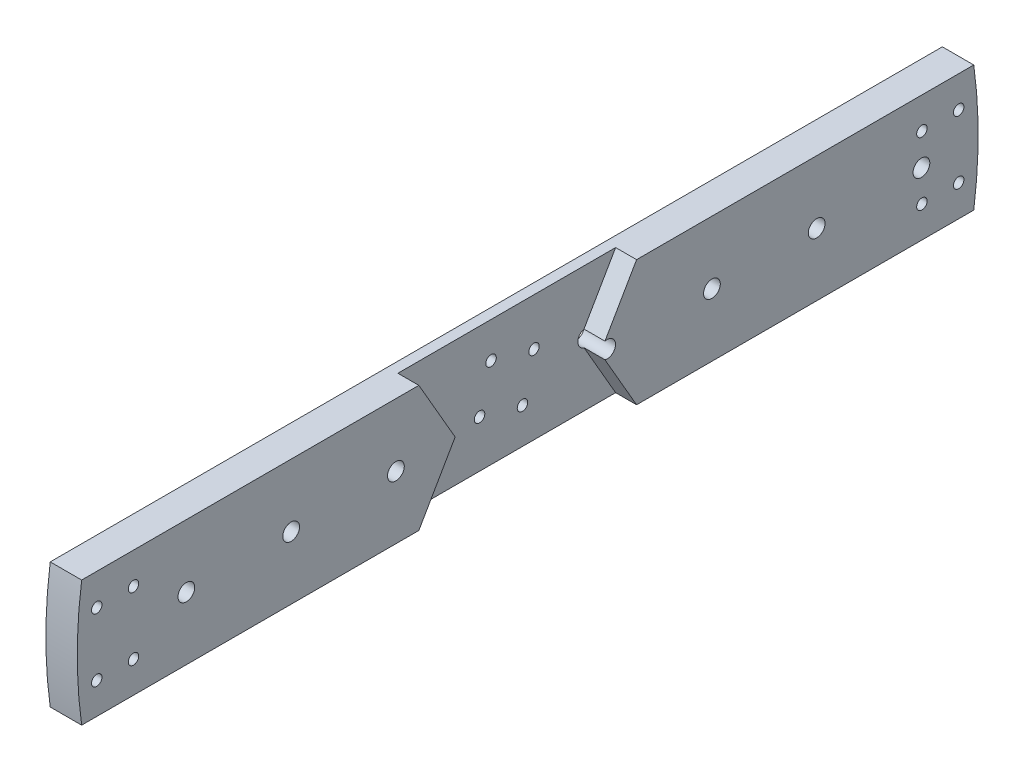
SolidWorks part; units mm, degrees
ref_plane "Front Plane" through (0, 0, 0) normal (0, 0, 1) x (1, 0, 0)
ref_plane "Top Plane" through (0, 0, 0) normal (0, 1, 0) x (1, 0, 0)
ref_plane "Right Plane" through (0, 0, 0) normal (1, 0, 0) x (0, 0, -1)
sketch "Sketch1" plane through (0, 0, 0) normal (1, 0, 0) x (0, 0, -1)
  circle A0 centre (0, 0) radius 273.05
  point P0 (0, 0)
  dimension "D1" = 546.1
curve "Helix/Spiral1"
sketch "Sketch2" plane through (0, 0, 0) normal (1, 0, 0) x (0, 0, -1)
  line L0 (-273.05, 0) -> (273.05, 0) construction
  line L1 (-270.3788, -38.1) -> (270.3788, -38.1)
  line L3 (-270.3788, 38.1) -> (270.3788, 38.1)
  line L4 (270.3788, -38.1) -> (270.3788, 38.1) construction
  line L5 (-270.3788, -38.1) -> (270.3788, 38.1) construction
  line L6 (-270.3788, 38.1) -> (270.3788, -38.1) construction
  line L7 (273.05, 0) -> (228.6, 0) construction
  line L8 (38.1, -38.1) -> (-38.1, -38.1)
  line L9 (38.1, -38.1) -> (38.1, 38.1)
  line L10 (38.1, 38.1) -> (-38.1, 38.1)
  line L11 (-38.1, -38.1) -> (-38.1, 38.1)
  line L12 (38.1, -38.1) -> (-38.1, 38.1) construction
  line L13 (38.1, 38.1) -> (-38.1, -38.1) construction
  line L14 (226.3636, 31.8977) -> (270.3788, 38.1)
  line L15 (0, 0) -> (65.9911, 38.1)
  line L16 (273.05, 0) -> (250.825, 0)
  line L17 (250.825, 0) -> (228.6, 0)
  line L20 (0, 38.1) -> (0, -38.1) construction
  circle A0 centre (0, 0) radius 273.05 construction
  circle A3 centre (175.1536, 0) radius 5.08
  circle A4 centre (111.6538, 0) radius 5.08
  circle A6 centre (-79.9039, 0) radius 5.08
  circle A7 centre (-143.4037, 0) radius 5.08
  circle A8 centre (-206.9035, 0) radius 5.08
  circle A9 centre (0, 0) radius 273.05
  circle A10 centre (0, 0) radius 228.6
  arc A11 (247.9144, -38.1) -> (250.825, 0) centre (0, 0) ccw
  arc A12 (236.6653, -38.1) -> (239.7125, 0) centre (0, 0) ccw
  arc A13 (259.1518, -38.1) -> (261.9375, 0) centre (0, 0) ccw
  circle A14 centre (238.9495, -19.1108) radius 3.175
  circle A15 centre (261.2401, -19.1009) radius 3.175
  circle A16 centre (238.9495, 19.1108) radius 3.175
  circle A17 centre (261.2401, 19.1009) radius 3.175
  circle A38 centre (-261.2401, -19.1009) radius 3.175
  circle A39 centre (-238.9495, -19.1108) radius 3.175
  circle A40 centre (-238.9495, 19.1108) radius 3.175
  circle A41 centre (-261.2401, 19.1009) radius 3.175
  circle A42 centre (238.6534, 0) radius 5.08
  circle A43 centre (48.154, 0) radius 5.08
  spline S0 degree 3 poles (1713.559, -1905.8938) (534.0732, 693.9874) (-223.0551, 401.0665) (-269.548, 35.479) (-270.2351, 26.6018) (-270.7354, 8.8553) (-270.5486, -0.014) (-269.3091, -17.6591) (-268.2565, -26.435) (-265.302, -43.8093) (-263.4, -52.4078) (-258.7715, -69.3456) (-256.0449, -77.6849) (-249.7993, -94.026) (-246.2803, -102.0277) (-238.4899, -117.6188) (-234.2185, -125.2082) (-224.9698, -139.9043) (-219.9927, -147.0111) (-209.3859, -160.6772) (-203.7564, -167.2365) (-191.904, -179.7483) (-185.6812, -185.7009) (-172.707, -196.9463) (-165.9555, -202.2392) (-151.993, -212.1193) (-144.782, -216.7065) (-129.9734, -225.1361) (-122.3759, -228.9786) (-106.8706, -235.8874) (-98.9629, -238.9537) (-82.9159, -244.2867) (-74.7766, -246.5532) (-58.3469, -250.2707) (-50.0565, -251.7217) (-33.4056, -253.8004) (-25.0451, -254.4281) (0.0194, -255.0766) (16.7059, -253.859) (49.3942, -248.2211) (65.3954, -243.8012) (96.1098, -231.978) (110.8224, -224.5751) (138.4151, -207.1169) (151.2947, -197.062) (174.756, -174.7274) (185.3372, -162.4484) (203.8323, -136.1719) (211.7458, -122.1753) (224.6444, -93.0285) (229.6293, -77.8791) (236.5265, -47.0269) (238.4389, -31.3249) (239.1676, 0.0209) (237.9841, 15.6639) (232.6175, 46.292) (228.4347, 61.2764) (217.2794, 90.0231) (210.3075, 103.7847) (193.8882, 129.5778) (184.4415, 141.6087) (163.4771, 163.5077) (151.96, 173.3753) (127.3322, 190.6053) (114.2221, 197.9675) (86.9391, 209.947) (72.7668, 214.5641) (43.9218, 220.9235) (29.2498, 222.6658) (-0.0224, 223.2586) (-14.6219, 222.1093) (-43.1898, 217.014) (-57.1575, 213.0682) (-83.9364, 202.5809) (-96.747, 196.0398) (-120.7405, 180.6596) (-131.9228, 171.821) (-152.2594, 152.2267) (-161.4133, 141.4716) (-177.3783, 118.4924) (-184.1892, 106.2689) (-195.2496, 80.8496) (-199.499, 67.6544) (-205.3205, 40.8166) (-206.8927, 27.1748) (-207.3497, -0.0239) (-206.2345, -13.5799) (-201.4104, -40.0875) (-197.7017, -53.0385) (-187.8824, -77.8497) (-181.7721, -89.7093) (-167.431, -111.9032) (-159.2005, -122.2368) (-140.9763, -141.0111) (-130.9832, -149.4513) (-109.6526, -164.1513) (-98.3157, -170.4109) (-74.7601, -180.5522) (-62.5421, -184.4338) (-37.7115, -189.7176) (-25.0997, -191.1197) (0.0254, -191.4407) (12.5379, -190.3597) (36.9853, -185.8068) (48.9195, -182.3352) (71.7629, -173.1838) (82.6716, -167.5045) (103.0659, -154.2023) (112.5509, -146.5799) (129.7628, -129.7259) (137.4893, -120.4948) (150.9243, -100.8128) (156.6326, -90.3625) (165.8548, -68.6707) (169.3687, -57.4297) (174.1146, -34.6064) (175.3466, -23.0246) (175.5317, 0.0268) (174.4849, 11.496) (170.2033, 33.8831) (166.9687, 44.8005) (158.4853, 65.6762) (153.2368, 75.634) (140.9737, 94.2285) (133.9594, 102.865) (118.4755, 118.5145) (110.0064, 125.5274) (91.973, 137.6974) (82.4093, 142.8543) (62.5812, 151.1574) (52.3173, 154.3035) (31.5012, 158.5116) (20.9496, 159.5736) (-0.0283, 159.6228) (-10.454, 158.6101) (-30.7809, 154.5997) (-40.6816, 151.6022) (-59.5895, 143.7868) (-68.5963, 138.9692) (-85.3912, 127.745) (-93.179, 121.3389) (-107.2662, 107.2251) (-113.5654, 99.518) (-124.4704, 83.1333) (-129.076, 74.4561) (-136.46, 56.4917) (-139.2383, 47.205) (-142.9086, 28.3961) (-143.8005, 18.8745) (-143.7138, -0.0298) (-142.7353, -9.412) (-138.9961, -27.6786) (-136.2357, -36.5626) (-129.0882, -53.5028) (-124.7015, -61.5586) (-114.5164, -76.5539) (-108.7183, -83.4931) (-95.9747, -96.0179) (-89.0296, -101.6034) (-74.2935, -111.2434) (-66.5029, -115.2977) (-50.4023, -121.7626) (-42.0926, -124.1732) (-25.2909, -127.3056) (-16.7994, -128.0275) (0.0313, -127.8049) (8.37, -126.8605) (24.5764, -123.3926) (32.4436, -120.8692) (47.416, -114.3897) (54.5209, -110.4338) (67.7166, -101.2877) (73.8071, -96.0978) (84.7697, -84.7244) (89.6415, -78.5412) (98.0164, -65.4537) (101.5194, -58.5497) (107.0652, -44.3128) (109.108, -36.9802) (111.7026, -22.1858) (112.2544, -14.7244) (111.8959, 0.0328) (110.9857, 7.3281) (107.789, 21.4742) (105.5027, 28.3246) (99.6911, 41.3293) (96.1662, 47.4832) (88.0591, 58.8793) (83.4773, 64.1212) (73.474, 73.5214) (68.0528, 77.6795) (56.6139, 84.7894) (50.5965, 87.7411) (38.2233, 92.3678) (31.8679, 94.0429) (19.0807, 96.0996) (12.6493, 96.4814) (-0.0343, 95.9869) (-6.2861, 95.1109) (-18.3719, 92.1854) (-24.2057, 90.1362) (-35.2426, 84.9926) (-40.4455, 81.8985) (-50.042, 74.8304) (-54.4353, 70.8568) (-62.2731, 62.2236) (-65.7175, 57.5644) (-71.5624, 47.7741) (-73.9627, 42.6433) (-77.6704, 32.1339) (-78.9777, 26.7555) (-80.4966, 15.9755) (-80.7083, 10.5742) (-80.078, -0.0357) (-79.2361, -5.2441) (-76.5819, -15.2697) (-74.7697, -20.0867) (-70.2941, -29.1558) (-67.6308, -33.4079) (-61.6018, -41.2046) (-58.2362, -44.7493) (-50.9732, -51.0248) (-47.076, -53.7555) (-38.9344, -58.3354) (-34.6901, -60.1844) (-26.0444, -62.973) (-21.6431, -63.9126) (-12.8704, -64.8936) (-8.4992, -64.9352) (0.0372, -64.169) (4.2021, -63.3613) (12.1675, -60.9783) (15.9677, -59.4032) (23.0691, -55.5955) (26.3702, -53.3632) (32.3673, -48.3731) (35.0634, -45.6157) (39.7765, -39.7228) (41.7936, -36.5876) (45.1084, -30.0946) (46.4061, -26.7369) (48.2756, -19.9549) (48.8474, -16.5308) (49.2906, -9.7652) (49.1622, -6.4241) (48.26, 0.0387) (47.4865, 3.1602) (45.3747, 9.0652) (44.0367, 11.8487) (40.897, 16.9824) (39.0955, 19.3325) (35.1445, 23.53) (32.9952, 25.3774) (28.4724, 28.5282) (26.0992, 29.8316) (21.2548, 31.8814) (18.7837, 32.6278) (13.8655, 33.5782) (11.4184, 33.7823) (6.6601, 33.6877) (4.349, 33.3891) (-0.0402, 32.3511) (-2.1182, 31.6117) (-5.963, 29.7712) (-7.7297, 28.6702) (-10.8957, 26.1985) (-12.2948, 24.8279) (-14.6927, 21.9159) (-15.6915, 20.3746) (-17.2799, 17.222) (-17.8696, 15.6108) (-18.6544, 12.415) (-18.8495, 10.8305) (-19.5185, -54.4432) (292.291, -18.3242) (-1035.3772, 2814.9913) knots -0.153771 -0.153771 -0.153771 -0.153771 0.003906 0.003906 0.007813 0.007813 0.011719 0.011719 0.015625 0.015625 0.019531 0.019531 0.023438 0.023438 0.027344 0.027344 0.03125 0.03125 0.035156 0.035156 0.039063 0.039063 0.042969 0.042969 0.046875 0.046875 0.050781 0.050781 0.054688 0.054688 0.058594 0.058594 0.0625 0.0625 0.066406 0.066406 0.070313 0.070313 0.078125 0.078125 0.085938 0.085938 0.09375 0.09375 0.101563 0.101563 0.109375 0.109375 0.117188 0.117188 0.125 0.125 0.132813 0.132813 0.140625 0.140625 0.148438 0.148438 0.15625 0.15625 0.164063 0.164063 0.171875 0.171875 0.179688 0.179688 0.1875 0.1875 0.195313 0.195313 0.203125 0.203125 0.210938 0.210938 0.21875 0.21875 0.226563 0.226563 0.234375 0.234375 0.242188 0.242188 0.25 0.25 0.257813 0.257813 0.265625 0.265625 0.273438 0.273438 0.28125 0.28125 0.289063 0.289063 0.296875 0.296875 0.304688 0.304688 0.3125 0.3125 0.320313 0.320313 0.328125 0.328125 0.335938 0.335938 0.34375 0.34375 0.351563 0.351563 0.359375 0.359375 0.367188 0.367188 0.375 0.375 0.382813 0.382813 0.390625 0.390625 0.398438 0.398438 0.40625 0.40625 0.414063 0.414063 0.421875 0.421875 0.429688 0.429688 0.4375 0.4375 0.445312 0.445312 0.453125 0.453125 0.460937 0.460937 0.46875 0.46875 0.476562 0.476562 0.484375 0.484375 0.492187 0.492187 0.5 0.5 0.507812 0.507812 0.515625 0.515625 0.523437 0.523437 0.53125 0.53125 0.539062 0.539062 0.546875 0.546875 0.554687 0.554687 0.5625 0.5625 0.570312 0.570312 0.578125 0.578125 0.585937 0.585937 0.59375 0.59375 0.601562 0.601562 0.609375 0.609375 0.617187 0.617187 0.625 0.625 0.632812 0.632812 0.640625 0.640625 0.648437 0.648437 0.65625 0.65625 0.664062 0.664062 0.671875 0.671875 0.679687 0.679687 0.6875 0.6875 0.695312 0.695312 0.703125 0.703125 0.710937 0.710937 0.71875 0.71875 0.726562 0.726562 0.734375 0.734375 0.742187 0.742187 0.75 0.75 0.757812 0.757812 0.765625 0.765625 0.773438 0.773438 0.78125 0.78125 0.789062 0.789062 0.796875 0.796875 0.804688 0.804688 0.8125 0.8125 0.820312 0.820312 0.828125 0.828125 0.835938 0.835938 0.84375 0.84375 0.851562 0.851562 0.859375 0.859375 0.867188 0.867188 0.875 0.875 0.882812 0.882812 0.890625 0.890625 0.898438 0.898438 0.90625 0.90625 0.914062 0.914062 0.921875 0.921875 0.929688 0.929688 0.9375 0.9375 0.945312 0.945312 0.953125 0.953125 0.960938 0.960938 0.96875 0.96875 0.976562 0.976562 0.984375 0.984375 0.992188 0.992188 1.318271 1.318271 1.318271 1.318271 only from (-263.746, 70.6705) to (-18.4009, 4.9305) construction
  spline S1 degree 3 poles (-263.746, 70.6705) (-265.7393, 61.9539) (-267.3001, 53.155) (-269.548, 35.479) (-270.2351, 26.6018) (-270.7354, 8.8553) (-270.5486, -0.014) (-269.3091, -17.6591) (-268.2565, -26.435) (-265.302, -43.8093) (-263.4, -52.4078) (-258.7715, -69.3456) (-256.0449, -77.6849) (-249.7993, -94.026) (-246.2803, -102.0277) (-238.4899, -117.6188) (-234.2185, -125.2082) (-224.9698, -139.9043) (-219.9927, -147.0111) (-209.3859, -160.6772) (-203.7564, -167.2365) (-191.904, -179.7483) (-185.6812, -185.7009) (-172.707, -196.9463) (-165.9555, -202.2392) (-151.993, -212.1193) (-144.782, -216.7065) (-129.9734, -225.1361) (-122.3759, -228.9786) (-106.8706, -235.8874) (-98.9629, -238.9537) (-82.9159, -244.2867) (-74.7766, -246.5532) (-58.3469, -250.2707) (-50.0565, -251.7217) (-33.4056, -253.8004) (-25.0451, -254.4281) (0.0194, -255.0766) (16.7059, -253.859) (49.3942, -248.2211) (65.3954, -243.8012) (96.1098, -231.978) (110.8224, -224.5751) (138.4151, -207.1169) (151.2947, -197.062) (174.756, -174.7274) (185.3372, -162.4484) (203.8323, -136.1719) (211.7458, -122.1753) (224.6444, -93.0285) (229.6293, -77.8791) (236.5265, -47.0269) (238.4389, -31.3249) (239.1676, 0.0209) (237.9841, 15.6639) (232.6175, 46.292) (228.4347, 61.2764) (217.2794, 90.0231) (210.3075, 103.7847) (193.8882, 129.5778) (184.4415, 141.6087) (163.4771, 163.5077) (151.96, 173.3753) (127.3322, 190.6053) (114.2221, 197.9675) (86.9391, 209.947) (72.7668, 214.5641) (43.9218, 220.9235) (29.2498, 222.6658) (-0.0224, 223.2586) (-14.6219, 222.1093) (-43.1898, 217.014) (-57.1575, 213.0682) (-83.9364, 202.5809) (-96.747, 196.0398) (-120.7405, 180.6596) (-131.9228, 171.821) (-152.2594, 152.2267) (-161.4133, 141.4716) (-177.3783, 118.4924) (-184.1892, 106.2689) (-195.2496, 80.8496) (-199.499, 67.6544) (-205.3205, 40.8166) (-206.8927, 27.1748) (-207.3497, -0.0239) (-206.2345, -13.5799) (-201.4104, -40.0875) (-197.7017, -53.0385) (-187.8824, -77.8497) (-181.7721, -89.7093) (-167.431, -111.9032) (-159.2005, -122.2368) (-140.9763, -141.0111) (-130.9832, -149.4513) (-109.6526, -164.1513) (-98.3157, -170.4109) (-74.7601, -180.5522) (-62.5421, -184.4338) (-37.7115, -189.7176) (-25.0997, -191.1197) (0.0254, -191.4407) (12.5379, -190.3597) (36.9853, -185.8068) (48.9195, -182.3352) (71.7629, -173.1838) (82.6716, -167.5045) (103.0659, -154.2023) (112.5509, -146.5799) (129.7628, -129.7259) (137.4893, -120.4948) (150.9243, -100.8128) (156.6326, -90.3625) (165.8548, -68.6707) (169.3687, -57.4297) (174.1146, -34.6064) (175.3466, -23.0246) (175.5317, 0.0268) (174.4849, 11.496) (170.2033, 33.8831) (166.9687, 44.8005) (158.4853, 65.6762) (153.2368, 75.634) (140.9737, 94.2285) (133.9594, 102.865) (118.4755, 118.5145) (110.0064, 125.5274) (91.973, 137.6974) (82.4093, 142.8543) (62.5812, 151.1574) (52.3173, 154.3035) (31.5012, 158.5116) (20.9496, 159.5736) (-0.0283, 159.6228) (-10.454, 158.6101) (-30.7809, 154.5997) (-40.6816, 151.6022) (-59.5895, 143.7868) (-68.5963, 138.9692) (-85.3912, 127.745) (-93.179, 121.3389) (-107.2662, 107.2251) (-113.5654, 99.518) (-124.4704, 83.1333) (-129.076, 74.4561) (-136.46, 56.4917) (-139.2383, 47.205) (-142.9086, 28.3961) (-143.8005, 18.8745) (-143.7138, -0.0298) (-142.7353, -9.412) (-138.9961, -27.6786) (-136.2357, -36.5626) (-129.0882, -53.5028) (-124.7015, -61.5586) (-114.5164, -76.5539) (-108.7183, -83.4931) (-95.9747, -96.0179) (-89.0296, -101.6034) (-74.2935, -111.2434) (-66.5029, -115.2977) (-50.4023, -121.7626) (-42.0926, -124.1732) (-25.2909, -127.3056) (-16.7994, -128.0275) (0.0313, -127.8049) (8.37, -126.8605) (24.5764, -123.3926) (32.4436, -120.8692) (47.416, -114.3897) (54.5209, -110.4338) (67.7166, -101.2877) (73.8071, -96.0978) (84.7697, -84.7244) (89.6415, -78.5412) (98.0164, -65.4537) (101.5194, -58.5497) (107.0652, -44.3128) (109.108, -36.9802) (111.7026, -22.1858) (112.2544, -14.7244) (111.8959, 0.0328) (110.9857, 7.3281) (107.789, 21.4742) (105.5027, 28.3246) (99.6911, 41.3293) (96.1662, 47.4832) (88.0591, 58.8793) (83.4773, 64.1212) (73.474, 73.5214) (68.0528, 77.6795) (56.6139, 84.7894) (50.5965, 87.7411) (38.2233, 92.3678) (31.8679, 94.0429) (19.0807, 96.0996) (12.6493, 96.4814) (-0.0343, 95.9869) (-6.2861, 95.1109) (-18.3719, 92.1854) (-24.2057, 90.1362) (-35.2426, 84.9926) (-40.4455, 81.8985) (-50.042, 74.8304) (-54.4353, 70.8568) (-62.2731, 62.2236) (-65.7175, 57.5644) (-71.5624, 47.7741) (-73.9627, 42.6433) (-77.6704, 32.1339) (-78.9777, 26.7555) (-80.4966, 15.9755) (-80.7083, 10.5742) (-80.078, -0.0357) (-79.2361, -5.2441) (-76.5819, -15.2697) (-74.7697, -20.0867) (-70.2941, -29.1558) (-67.6308, -33.4079) (-61.6018, -41.2046) (-58.2362, -44.7493) (-50.9732, -51.0248) (-47.076, -53.7555) (-38.9344, -58.3354) (-34.6901, -60.1844) (-26.0444, -62.973) (-21.6431, -63.9126) (-12.8704, -64.8936) (-8.4992, -64.9352) (0.0372, -64.169) (4.2021, -63.3613) (12.1675, -60.9783) (15.9677, -59.4032) (23.0691, -55.5955) (26.3702, -53.3632) (32.3673, -48.3731) (35.0634, -45.6157) (39.7765, -39.7228) (41.7936, -36.5876) (45.1084, -30.0946) (46.4061, -26.7369) (48.2756, -19.9549) (48.8474, -16.5308) (49.2906, -9.7652) (49.1622, -6.4241) (48.26, 0.0387) (47.4865, 3.1602) (45.3747, 9.0652) (44.0367, 11.8487) (40.897, 16.9824) (39.0955, 19.3325) (35.1445, 23.53) (32.9952, 25.3774) (28.4724, 28.5282) (26.0992, 29.8316) (21.2548, 31.8814) (18.7837, 32.6278) (13.8655, 33.5782) (11.4184, 33.7823) (6.6601, 33.6877) (4.349, 33.3891) (-0.0402, 32.3511) (-2.1182, 31.6117) (-5.963, 29.7712) (-7.7297, 28.6702) (-10.8957, 26.1985) (-12.2948, 24.8279) (-14.6927, 21.9159) (-15.6915, 20.3746) (-17.2799, 17.222) (-17.8696, 15.6108) (-18.6544, 12.415) (-18.8495, 10.8305) (-18.8808, 7.776) (-18.7171, 6.306) (-18.4009, 4.9305) knots 0 0 0 0 0.003906 0.003906 0.007813 0.007813 0.011719 0.011719 0.015625 0.015625 0.019531 0.019531 0.023438 0.023438 0.027344 0.027344 0.03125 0.03125 0.035156 0.035156 0.039063 0.039063 0.042969 0.042969 0.046875 0.046875 0.050781 0.050781 0.054688 0.054688 0.058594 0.058594 0.0625 0.0625 0.066406 0.066406 0.070313 0.070313 0.078125 0.078125 0.085938 0.085938 0.09375 0.09375 0.101563 0.101563 0.109375 0.109375 0.117188 0.117188 0.125 0.125 0.132813 0.132813 0.140625 0.140625 0.148438 0.148438 0.15625 0.15625 0.164063 0.164063 0.171875 0.171875 0.179688 0.179688 0.1875 0.1875 0.195313 0.195313 0.203125 0.203125 0.210938 0.210938 0.21875 0.21875 0.226563 0.226563 0.234375 0.234375 0.242188 0.242188 0.25 0.25 0.257813 0.257813 0.265625 0.265625 0.273438 0.273438 0.28125 0.28125 0.289063 0.289063 0.296875 0.296875 0.304688 0.304688 0.3125 0.3125 0.320313 0.320313 0.328125 0.328125 0.335938 0.335938 0.34375 0.34375 0.351563 0.351563 0.359375 0.359375 0.367188 0.367188 0.375 0.375 0.382813 0.382813 0.390625 0.390625 0.398438 0.398438 0.40625 0.40625 0.414063 0.414063 0.421875 0.421875 0.429688 0.429688 0.4375 0.4375 0.445312 0.445312 0.453125 0.453125 0.460937 0.460937 0.46875 0.46875 0.476562 0.476562 0.484375 0.484375 0.492187 0.492187 0.5 0.5 0.507812 0.507812 0.515625 0.515625 0.523437 0.523437 0.53125 0.53125 0.539062 0.539062 0.546875 0.546875 0.554687 0.554687 0.5625 0.5625 0.570312 0.570312 0.578125 0.578125 0.585937 0.585937 0.59375 0.59375 0.601562 0.601562 0.609375 0.609375 0.617187 0.617187 0.625 0.625 0.632812 0.632812 0.640625 0.640625 0.648437 0.648437 0.65625 0.65625 0.664062 0.664062 0.671875 0.671875 0.679687 0.679687 0.6875 0.6875 0.695312 0.695312 0.703125 0.703125 0.710937 0.710937 0.71875 0.71875 0.726562 0.726562 0.734375 0.734375 0.742187 0.742187 0.75 0.75 0.757812 0.757812 0.765625 0.765625 0.773438 0.773438 0.78125 0.78125 0.789062 0.789062 0.796875 0.796875 0.804688 0.804688 0.8125 0.8125 0.820312 0.820312 0.828125 0.828125 0.835938 0.835938 0.84375 0.84375 0.851562 0.851562 0.859375 0.859375 0.867188 0.867188 0.875 0.875 0.882812 0.882812 0.890625 0.890625 0.898438 0.898438 0.90625 0.90625 0.914062 0.914062 0.921875 0.921875 0.929688 0.929688 0.9375 0.9375 0.945312 0.945312 0.953125 0.953125 0.960938 0.960938 0.96875 0.96875 0.976562 0.976562 0.984375 0.984375 0.992188 0.992188 1 1 1 1 construction
  point P0 (0, 0)
  point P26 (0, 0)
  point P37 (250.825, 0)
  point P40 (239.7125, 0)
  point P45 (261.9375, 0)
  point P46 (238.9495, -19.1108)
  point P64 (261.2401, -19.1009)
  dimension "D2" = 10.16
  dimension "D4" = 457.2
  dimension "D5" = 6.35
  dimension "D1" = 76.2
  dimension "D3" = 76.2
  dimension "D6" = 60
extrude "Boss-Extrude1" add sketch "Sketch2" along normal blind 19.05 contours L3 A10 L1 L11 A6 A7 A8 | A10 L3 L9 L1 A3 A4 | A15 A13 L1 A9 L14 A10 L17 L16 A16 A17 | A10 L14 L3 | A14 A12 L17 A10 L1 | A14 A12 L1 A11 L17 | A15 A13 L16 A11 L1 | A15 A13 L1 A9 L16 | A10 L3 A9 L1 A41 A40 A38 A39 | L9 L15 L3 | L9 L8 L11 L10 region at (0, 0, 132.6396) region at (0, -0.5263, -134.563) region at (0, 0, 249.8366) region at (0, -20.2173, -232.6685) region at (0, 32.7323, -47.397) region at (0, -19.733, -244.5457) region at (0, 17.9363, -251.0195) region at (0, -19.078, -266.739) region at (0, 36.0332, -240.7246) region at (0, -19.0886, -255.259)
sketch "Sketch3" plane through (19.05, 0, 0) normal (1, 0, 0) x (0, 0, -1)
  line L0 (-21.997, -38.1) -> (-65.9911, 38.1)
  line L1 (-21.997, -38.1) -> (65.9911, -38.1)
  line L2 (-65.9911, 38.1) -> (21.997, 38.1)
  line L3 (65.9911, -38.1) -> (21.997, 38.1)
  line L4 (-270.3788, -38.1) -> (270.3788, -38.1) construction
  line L5 (-270.3788, 38.1) -> (270.3788, 38.1) construction
  line L6 (-65.9911, 38.1) -> (65.9911, -38.1)
  line L7 (0, 263.0844) -> (0, -263.0844) construction
  line L8 (65.9911, 38.1) -> (-21.997, 38.1)
  line L9 (-65.9911, -38.1) -> (-21.997, 38.1)
  line L10 (21.997, -38.1) -> (-65.9911, -38.1)
  line L11 (21.997, -38.1) -> (65.9911, 38.1)
  line L12 (0, 0) -> (65.9911, 38.1) construction
  line L13 (0, 0) -> (0, 38.1)
  line L14 (9.525, -16.4978) -> (16.4978, 9.525)
  line L15 (9.525, -16.4978) -> (-16.4978, -9.525)
  line L16 (16.4978, 9.525) -> (-9.525, 16.4978)
  line L17 (-16.4978, -9.525) -> (-9.525, 16.4978)
  line L18 (-21.997, 38.1) -> (0, 0)
  line L19 (0, 0) -> (32.9956, 19.05)
  circle A0 centre (16.4978, 9.525) radius 3.175
  circle A1 centre (-9.525, 16.4978) radius 3.175
  circle A2 centre (-16.4978, -9.525) radius 3.175
  circle A3 centre (9.525, -16.4978) radius 3.175
  point P8 (0, 0)
  line M22 (270.3788, 38.1) -> (-270.3788, 38.1)
  line M24 (-270.3788, -38.1) -> (270.3788, -38.1)
  dimension "D6" = 6.35
  dimension "D1" = 60
  dimension "D2" = 76.2
  dimension "D3" = 60
  dimension "D4" = 26.0228
  dimension "D5" = 90
extrude "Cut-Extrude1" cut sketch "Sketch3" against normal blind 12.7 contours L12 L3 L11 | L3 L12 M22 | A0 L19 L3 L13 L16 M22 | A1 L16 L13 L8 L18 | A1 L18 L9 L6 L17 | L6 L9 L2 | L0 L9 L6 | A3 L15 A2 L17 L6 L9 L0 L11 L14 M24 | L9 L0 M24 | L11 L1 L6 | L11 L6 L3 | A0 L14 L6 L11 L3 L19 | A0 L19 L6 L14 | A3 L14 L6 L17 A2 L15 | A1 L17 L6 L18 | A1 L18 L13 L16 | A0 L16 L13 L19 region at (19.05, -25.4, 43.9941) region at (19.05, -16.3618, 9.6478) region at (19.05, 19.05, 47.6603) region at (19.05, -31.75, -40.3279) region at (19.05, 31.75, 40.3279) region at (19.05, 21.3346, 20.7498) region at (19.05, -19.05, -47.6603) region at (19.05, -0.2798, -28.4047) region at (19.05, 28.6372, 8.1015) region at (19.05, 7.4033, 7.0705) region at (19.05, -5.7799, 2.8511) region at (19.05, 19.05, -47.6603) region at (19.05, 0.5999, -9.3212) region at (19.05, 24.7391, -13.96) region at (19.05, 7.7725, -5.1802) region at (19.05, 9.8249, 2.8762) region at (19.05, 31.75, -40.3279)
extrude "Cut-Extrude2" cut sketch "Sketch3<3>" against normal through all contours L19 A0 L16 | L16 A0 L19 | L19 A0 L14 | L14 A0 L19 | L14 A3 L15 | L15 A3 L14 | L15 A2 L17 | L17 A2 L15 | L16 A1 L18 | L18 A1 L17 | L17 A1 L18 | L18 A1 L16 region at (19.05, 17.8147, 8.5145) region at (19.05, 16.2811, 11.1707) region at (19.05, -8.5722, 14.8474) region at (19.05, -9.8426, 17.0479) region at (19.05, 14.4527, 9.2558) region at (19.05, -17.0479, -9.8426) region at (19.05, -14.8474, -8.5722) region at (19.05, 7.8886, -15.2421) region at (19.05, 8.5145, -17.8147) region at (19.05, 15.2421, 7.8886) region at (19.05, 9.2558, -14.4527) region at (19.05, 11.1707, -16.2811)
sketch "Sketch3<3>" plane through (19.05, 0, 0) normal (1, 0, 0) x (0, 0, -1) same geometry as "Sketch3"
